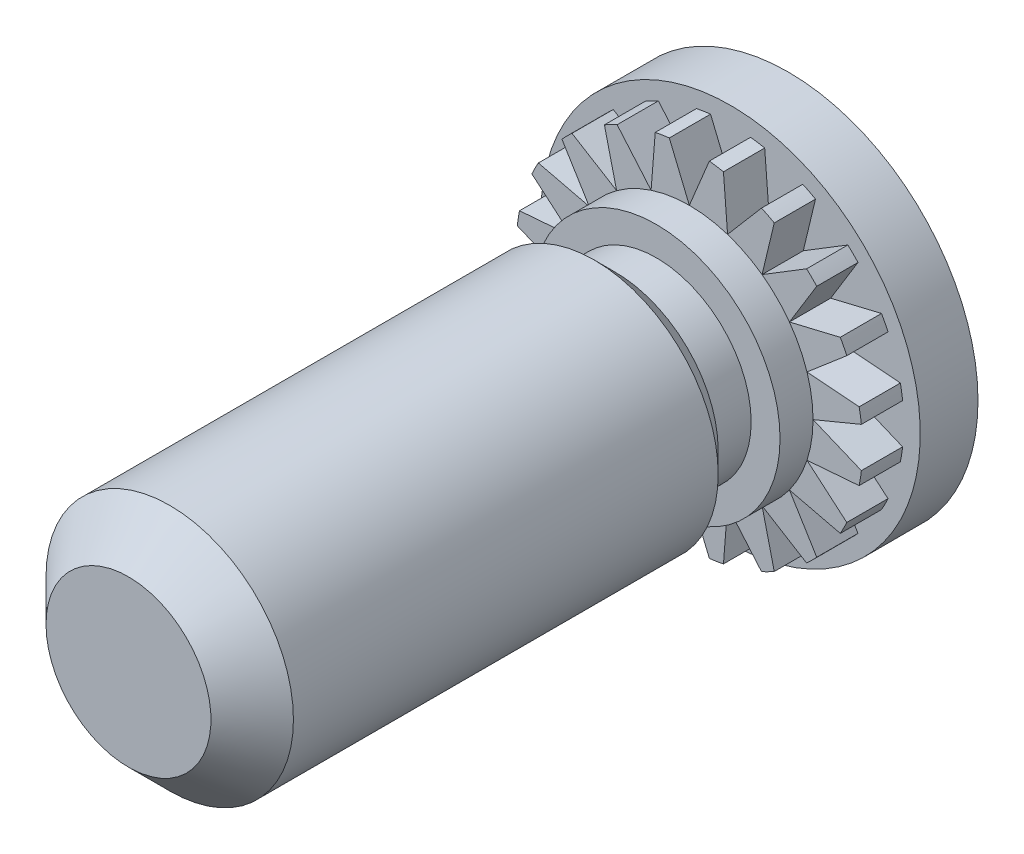
SolidWorks part; units mm, degrees
ref_plane "Спереди" through (0, 0, 0) normal (0, 0, 1) x (1, 0, 0)
ref_plane "Сверху" through (0, 0, 0) normal (0, 1, 0) x (1, 0, 0)
ref_plane "Справа" through (0, 0, 0) normal (1, 0, 0) x (0, 0, -1)
sketch "Эскиз1" plane through (0, 0, 0) normal (0, 0, 1) x (1, 0, 0)
  circle A0 centre (0, 0) radius 2.3
  dimension "D1" = 4.6
extrude "Вытянуть1" add sketch "Эскиз1" along normal blind 1.2
ref_axis "Ось1" through (0, 0, 10.6426) along (0, 0, -1)
sketch "Эскиз2" plane through (0, 0, 1.2) normal (0, 0, 1) x (1, 0, 0)
  circle A0 centre (0, 0) radius 1.5
  dimension "D1" = 3
extrude "Вытянуть2" add sketch "Эскиз2" along normal blind 1.5
sketch "Эскиз3" plane through (0, 0, 1.2) normal (0, 0, 1) x (1, 0, 0)
  line L0 (0, 0) -> (0, 2.3) construction
  line L1 (-0.3314, 2.3) -> (0.3314, 2.3)
  line L2 (0.3314, 2.3) -> (0, 1.5)
  line L3 (0, 1.5) -> (-0.3314, 2.3)
  circle A0 centre (0, 0) radius 2.3 construction
  circle A1 centre (0, 0) radius 1.5 construction
  dimension "D1" = 45
extrude "Вырез-Вытянуть1" cut sketch "Эскиз3" against normal blind 0.5
pattern_circular "Круговой массив1" count 20 over 360 about axis through (0, 0, 10.6426) along (0, 0, -1) of "Вырез-Вытянуть1"
sketch "Эскиз4" plane through (0, 0, 0) normal (0, 1, 0) x (1, 0, 0)
  line L0 (0, -1.85) -> (1.5, -1.85) construction
  line L1 (0, -4.6295) -> (0, 2.1879) construction
  line L2 (-1.5, -2.7) -> (1.5, -2.7) construction
  line L3 (1.5, -1.6) -> (1.15, -1.6)
  line L4 (1.5, -1.6) -> (1.5, -2.1)
  line L5 (1.5, -2.1) -> (1.15, -2.1)
  line L6 (1.15, -1.6) -> (1.15, -2.1)
  dimension "D1" = 0.5
  dimension "D2" = 0.6
  dimension "D3" = 1.5
  dimension "D4" = 0.35
revolve "Вырез-Повернуть1" cut sketch "Эскиз4" angle 360 about axis through (0, 0, 10.6426) along (0, 0, -1)
sketch "Эскиз6" plane through (0, 0, 0) normal (1, 0, 0) x (0, 0, -1)
  line L0 (-2.7, 0) -> (-8, 0)
  line L1 (-2.7, 1.5) -> (-2.7, -1.5) construction
  line L2 (-10.6426, 0) -> (0.6656, 0) construction
  line L3 (-8, 0) -> (-8, -1.5)
  line L4 (-8, -1.5) -> (-2.7, -1.5)
  line L5 (-2.7, -1.5) -> (-2.7, 0)
  line L6 (0, -2.3) -> (0, 2.3) construction
  dimension "D1" = 8
  dimension "D2" = 1.5
revolve "Повернуть1" add sketch "Эскиз6" angle 360 about L0
chamfer "Фаска2" distance 0.5 angle 45 1 edges at (-1.5, 0, 8)
sketch "Эскиз7" plane through (0, 0, 1.2) normal (0, 0, 1) x (1, 0, 0)
  circle A0 centre (0, 0) radius 2.1
  circle A1 centre (0, 0) radius 2.3
  arc A2 (-1.0781, 2.0317) -> (-1.5991, 1.6532) centre (0, 0) ccw construction
  dimension "D1" = 0.2
extrude "Вырез-Вытянуть2" cut sketch "Эскиз7" against normal up to surface (0.5 mm away) up to face at (-1.9266, 0.626, 0.7)
chamfer "Фаска3" distance 0.25 angle 45 1 edges at (1.5, 0, 2.1)
